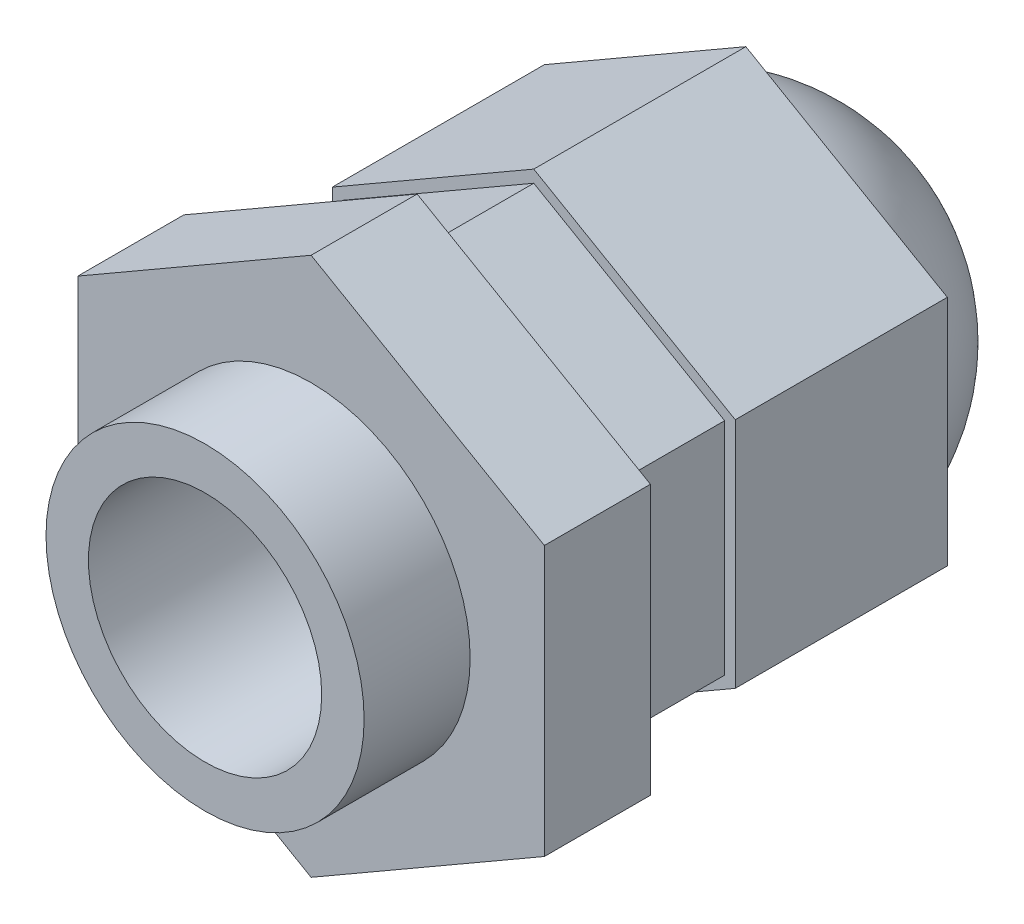
SolidWorks part; units mm, degrees
ref_plane "Спереди" through (0, 0, 0) normal (0, 0, 1) x (1, 0, 0)
ref_plane "Сверху" through (0, 0, 0) normal (0, 1, 0) x (1, 0, 0)
ref_plane "Справа" through (0, 0, 0) normal (1, 0, 0) x (0, 0, -1)
sketch "Эскиз1" plane through (0, 0, 0) normal (0, 0, 1) x (1, 0, 0)
  circle A0 centre (0, 0) radius 7.5
  dimension "D1" = 15
extrude "Вытянуть1" add sketch "Эскиз1" against normal blind 5
sketch "Эскиз2" plane through (0, 0, -5) normal (0, 0, -1) x (-1, 0, 0)
  line L0 (0, 0) -> (0, 16.4137) construction
  line L1 (0, 12.7017) -> (-11, 6.3509)
  line L2 (-11, 6.3509) -> (-11, -6.3509)
  line L3 (-11, -6.3509) -> (0, -12.7017)
  line L4 (0, -12.7017) -> (11, -6.3509)
  line L5 (11, -6.3509) -> (11, 6.3509)
  line L6 (11, 6.3509) -> (0, 12.7017)
  circle A0 centre (0, 0) radius 11 construction
  dimension "D1" = 22
extrude "Вытянуть2" add sketch "Эскиз2" along normal blind 5
sketch "Эскиз3" plane through (0, 0, -10) normal (0, 0, -1) x (-1, 0, 0)
  circle A1 centre (0, 0) radius 7.5
  circle A2 centre (0, 0) radius 7.5
  dimension "D1" = 0
extrude "Вытянуть3" add sketch "Эскиз3" along normal blind 1
sketch "Эскиз4" plane through (0, 0, -11) normal (0, 0, -1) x (-1, 0, 0)
  line L1 (0, 10.3923) -> (-9, 5.1962)
  line L2 (-9, 5.1962) -> (-9, -5.1962)
  line L3 (-9, -5.1962) -> (0, -10.3923)
  line L4 (0, -10.3923) -> (9, -5.1962)
  line L5 (9, -5.1962) -> (9, 5.1962)
  line L6 (9, 5.1962) -> (0, 10.3923)
  circle A0 centre (0, 0) radius 9 construction
  dimension "D1" = 18
extrude "Вытянуть4" add sketch "Эскиз4" along normal blind 4.5
sketch "Эскиз5" plane through (0, 0, -15.5) normal (0, 0, -1) x (-1, 0, 0)
  line L1 (0, 10.9697) -> (-9.5, 5.4848)
  line L2 (-9.5, 5.4848) -> (-9.5, -5.4848)
  line L3 (-9.5, -5.4848) -> (0, -10.9697)
  line L4 (0, -10.9697) -> (9.5, -5.4848)
  line L5 (9.5, -5.4848) -> (9.5, 5.4848)
  line L6 (9.5, 5.4848) -> (0, 10.9697)
  circle A0 centre (0, 0) radius 9.5 construction
  dimension "D1" = 19
extrude "Вытянуть5" add sketch "Эскиз5" along normal blind 10
sketch "Эскиз6" plane through (0, 0, -25.5) normal (0, 0, -1) x (-1, 0, 0)
  circle A0 centre (0, 0) radius 9
  dimension "D1" = 18
extrude "Вытянуть6" add sketch "Эскиз6" along normal blind 0.1
dome "Купол1" faces to dome 1 distance 7 reverse direction no elliptical dome no face at (-9, 0, -25.6) parameters "D1"=7
sketch "Эскиз7" plane through (0, 0, 0) normal (0, 0, 1) x (1, 0, 0)
  circle A0 centre (0, 0) radius 5.5
  dimension "D1" = 11
extrude "Вырез-Вытянуть1" cut sketch "Эскиз7" against normal offset from surface (24.5 mm away) 1 up to face at (0, 0, -25.5)
sketch "Эскиз8" plane through (0, 0, -24.5) normal (0, 0, 1) x (1, 0, 0)
  circle A0 centre (0, 0) radius 4
  dimension "D1" = 8
extrude "Вырез-Вытянуть2" cut sketch "Эскиз8" against normal blind 20
ref_plane "Плоскость1" through (0, 0, -31) normal (0, 0, 1) x (1, 0, 0)
sketch "Эскиз9" plane through (0, 0, -31) normal (0, 0, 1) x (1, 0, 0)
  line L1 (-7.3475, -6.3279) -> (6.9277, -6.3279)
  line L2 (-7.3475, -6.3279) -> (-7.3475, 6.9877)
  line L3 (-7.3475, 6.9877) -> (6.9277, 6.9877)
  line L4 (6.9277, -6.3279) -> (6.9277, 6.9877)
extrude "Вырез-Вытянуть3" cut sketch "Эскиз9" against normal blind 20
